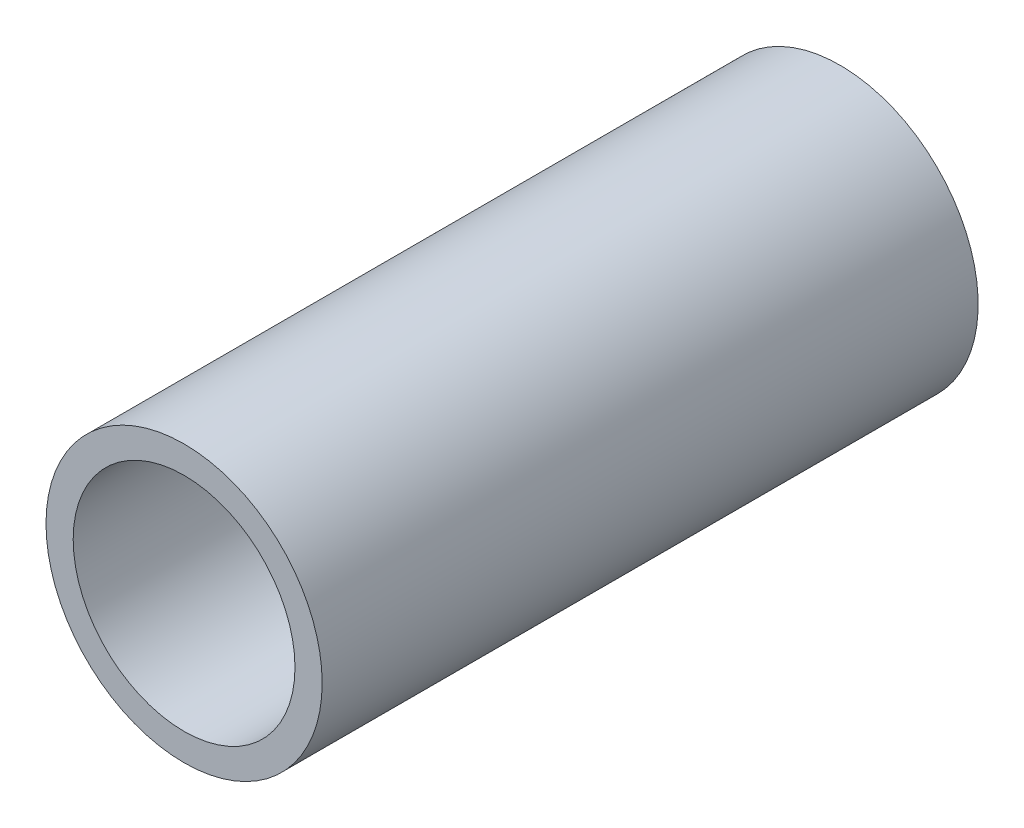
SolidWorks part; units mm, degrees
material "1060 Alloy"
ref_plane "Front Plane" through (0, 0, 0) normal (0, 0, 1) x (1, 0, 0)
ref_plane "Top Plane" through (0, 0, 0) normal (0, 1, 0) x (1, 0, 0)
ref_plane "Right Plane" through (0, 0, 0) normal (1, 0, 0) x (0, 0, -1)
sketch "Sketch1" plane through (0, 0, 0) normal (0, 0, 1) x (1, 0, 0)
  circle A0 centre (0, 0) radius 7.65
  circle A1 centre (0, 0) radius 9.525
  dimension "D1" = 15.3
  dimension "D2" = 19.05
extrude "Boss-Extrude1" add sketch "Sketch1" along normal blind 44.25
sketch "Sketch2" plane through (0, 0, 0) normal (0, 0, -1) x (-1, 0, 0)
  circle A0 centre (0, 0) radius 8.65
  circle A1 centre (0, 0) radius 7.65
  circle A3 centre (0, 0) radius 7.65 construction
  circle M2 centre (0, 0) radius 7.65
  dimension "D1" = 1
  dimension "D2" = 0
extrude "Cut-Extrude1" cut sketch "Sketch2" against normal blind 0.79 contours A0 M2 region at (8.4053, 0, 0)
sketch "Sketch3" plane through (0, 0, 0) normal (0, 0, -1) x (-1, 0, 0)
  circle A0 centre (0, 0) radius 9.525
  circle A1 centre (0, 0) radius 8.65
  circle A4 centre (0, 0) radius 9.525 construction
  circle A5 centre (0, 0) radius 8.65 construction
  dimension "D1" = 0
  dimension "D2" = 0
extrude "Boss-Extrude2" add sketch "Sketch3" along normal blind 1
thread "Thread1" pitch 0.25 method cut profile "Thread Profile1" start angle 0, offset 0, length 1.8, pitch 0.25, diameter 17.3
ref_plane "Plane1" through (8.65, 0, -1) normal (0, -1, 0) x (1, 0, 0)
sketch "Thread Profile1" plane through (8.65, 0, -1) normal (0, -1, 0) x (1, 0, 0)
  line L0 (0, 0) -> (0, 0.25) construction
  line L1 (0, 0) -> (0.1353, 0.0781)
  line L2 (0.1353, 0.0781) -> (0.1353, 0.1094)
  line L3 (0.1353, 0.1094) -> (0, 0.1875)
  line L4 (0.1353, 0.0937) -> (0, 0.0937) construction
  line L11 (0, 0) -> (0, 0.1875)
  point P2 (0, 0)
  dimension "Pitch" = 0.25
  dimension "Profile_Angle" = 60
  dimension "Profile_Land" = 0.0312
  dimension "Profile_Height" = 0.1353
